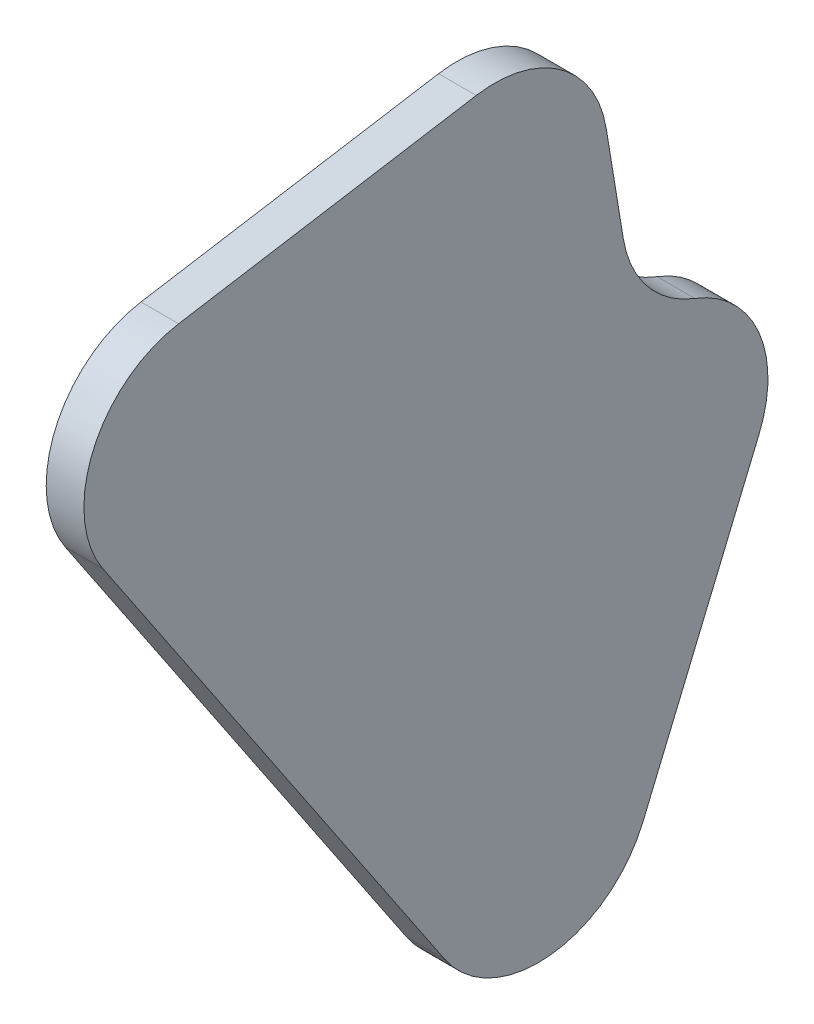
SolidWorks part; units mm, degrees
ref_plane "Front Plane" through (0, 0, 0) normal (0, 0, 1) x (1, 0, 0)
ref_plane "Top Plane" through (0, 0, 0) normal (0, 1, 0) x (1, 0, 0)
ref_plane "Right Plane" through (0, 0, 0) normal (1, 0, 0) x (0, 0, -1)
sketch "Sketch1" plane through (0, 0, 0) normal (1, 0, 0) x (0, 0, -1)
  line L0 (-1123.7457, 290.9693) -> (-1113.9432, 314.4016) construction
  line L1 (-1124.2575, 327.4793) -> (-1124.275, 327.4764) construction
  line L2 (-1126.832, 343.1442) -> (-1124.2575, 327.4793) construction
  line L3 (-1162.8393, 346.8792) -> (-1137.7756, 350.9984) construction
  line L4 (-1169.2024, 332.1706) -> (-1140.4405, 289.3355) construction
  line L5 (-1123.7457, 290.9693) -> (-1113.9432, 314.4016)
  line L6 (-1124.2575, 327.4793) -> (-1124.275, 327.4764)
  line L7 (-1126.832, 343.1442) -> (-1124.2575, 327.4793)
  line L8 (-1162.8393, 346.8792) -> (-1137.7756, 350.9984)
  line L9 (-1169.2024, 332.1706) -> (-1140.4405, 289.3355)
  circle A0 centre (-1132.5328, 294.6452) radius 9.525 construction
  circle A1 centre (-1122.7303, 318.0775) radius 9.525 construction
  circle A2 centre (-1136.2309, 341.5995) radius 9.525 construction
  circle A3 centre (-1161.2946, 337.4803) radius 9.525 construction
  arc A4 (-1140.4405, 289.3355) -> (-1123.7457, 290.9693) centre (-1132.5328, 294.6452) ccw
  arc A5 (-1113.9432, 314.4016) -> (-1124.275, 327.4764) centre (-1122.7303, 318.0775) ccw
  arc A6 (-1126.832, 343.1442) -> (-1137.7756, 350.9984) centre (-1136.2309, 341.5995) ccw
  arc A7 (-1162.8393, 346.8792) -> (-1169.2024, 332.1706) centre (-1161.2946, 337.4803) ccw
extrude "Boss-Extrude1" add sketch "Sketch1" along normal up to vertex (69.5961 mm away) from vertex at 66.4211
fillet "Fillet1" radius 9.525 4 edges at (66.4211, 327.4779, 1124.2662) (68.0086, 327.4793, 1124.2575) (68.0086, 327.4764, 1124.275) (69.5961, 327.4779, 1124.2662)
